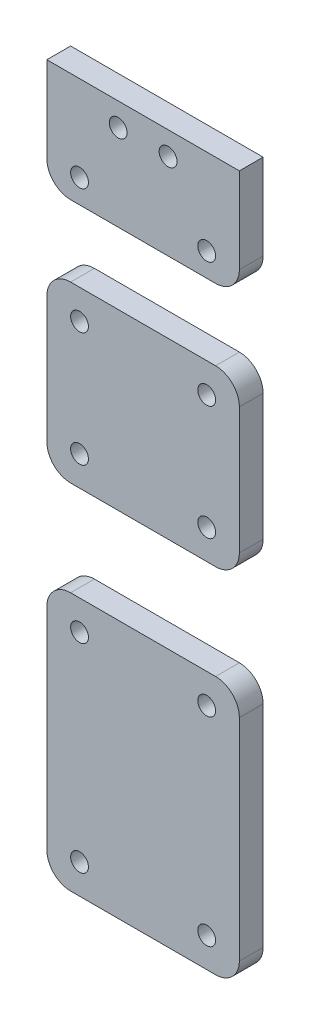
SolidWorks part; units mm, degrees
ref_plane "Front Plane" through (0, 0, 0) normal (0, 0, 1) x (1, 0, 0)
ref_plane "Top Plane" through (0, 0, 0) normal (0, 1, 0) x (1, 0, 0)
ref_plane "Right Plane" through (0, 0, 0) normal (1, 0, 0) x (0, 0, -1)
sketch "Sketch1" plane through (0, 0, 0) normal (0, 0, 1) x (1, 0, 0)
  line L0 (0, 1.5) -> (0, 14) construction
  line L1 (16.2, 1.5) -> (16.2, 14) construction
  line L2 (2, 47.74) -> (4, 47.74)
  line L3 (0, 1.5) -> (16.2, 1.5) construction
  line L4 (0, 14) -> (4, 14) construction
  line L5 (2, 26) -> (4, 26)
  line L6 (16.2, 85.59) -> (0, 85.59)
  line L7 (2, 70.385) -> (4, 70.385)
  line L8 (2, 55.74) -> (4, 55.74)
  line L9 (0, 28) -> (0, 45.74)
  line L10 (2, 76.385) -> (4, 76.385)
  line L11 (16.2, 28) -> (16.2, 45.74)
  line L12 (16.2, 57.74) -> (16.2, 68.385)
  line L13 (0, 57.74) -> (0, 68.385)
  line L14 (16.2, 78.385) -> (16.2, 85.59)
  line L15 (0, 78.385) -> (0, 85.59)
  line L16 (6, 70.385) -> (6, 76.385)
  line L17 (4, 55.74) -> (4, 47.74)
  line L18 (4, 70.385) -> (4, 76.385)
  line L19 (6, 55.74) -> (6, 47.74)
  line L20 (4, 26) -> (4, 14)
  line L21 (6, 26) -> (6, 14)
  line L22 (8.1, 1.5) -> (8.1, 85.59) construction
  line L23 (10.2, 26) -> (10.2, 14)
  line L24 (12.2, 26) -> (12.2, 14)
  line L25 (10.2, 55.74) -> (10.2, 47.74)
  line L26 (12.2, 55.74) -> (12.2, 47.74)
  line L27 (10.2, 70.385) -> (10.2, 76.385)
  line L28 (12.2, 70.385) -> (12.2, 76.385)
  line L29 (6, 26) -> (10.2, 26)
  line L30 (6, 14) -> (10.2, 14) construction
  line L31 (12.2, 14) -> (16.2, 14) construction
  line L32 (12.2, 26) -> (14.2, 26)
  line L33 (12.2, 47.74) -> (14.2, 47.74)
  line L34 (6, 47.74) -> (10.2, 47.74)
  line L35 (12.2, 76.385) -> (14.2, 76.385)
  line L36 (6, 76.385) -> (10.2, 76.385)
  line L37 (6, 70.385) -> (10.2, 70.385)
  line L38 (12.2, 70.385) -> (14.2, 70.385)
  line L39 (12.2, 55.74) -> (14.2, 55.74)
  line L40 (6, 55.74) -> (10.2, 55.74)
  line L41 (4, 14) -> (6, 14)
  line L42 (10.2, 14) -> (12.2, 14)
  circle A0 centre (13.45, 45.24) radius 0.75
  circle A1 centre (2.75, 67.885) radius 0.75
  circle A2 centre (13.45, 58.24) radius 0.75
  circle A3 centre (13.45, 78.385) radius 0.75
  circle A4 centre (2.75, 28.5) radius 0.75
  circle A5 centre (2.75, 78.385) radius 0.75
  circle A6 centre (2.75, 58.24) radius 0.75
  circle A7 centre (2.85, 11.5) radius 0.75 construction
  circle A8 centre (13.35, 11.5) radius 0.75 construction
  circle A9 centre (13.35, 5.5) radius 0.75 construction
  circle A10 centre (2.85, 5.5) radius 0.75 construction
  circle A11 centre (6, 83.635) radius 0.75
  circle A12 centre (13.45, 28.5) radius 0.75
  circle A13 centre (13.45, 67.885) radius 0.75
  circle A14 centre (10.2, 83.635) radius 0.75
  circle A15 centre (2.75, 45.24) radius 0.75
  arc A16 (0, 28) -> (2, 26) centre (2, 28) ccw
  arc A17 (16.2, 28) -> (14.2, 26) centre (14.2, 28) cw
  arc A18 (16.2, 45.74) -> (14.2, 47.74) centre (14.2, 45.74) ccw
  arc A19 (0, 45.74) -> (2, 47.74) centre (2, 45.74) cw
  arc A20 (0, 57.74) -> (2, 55.74) centre (2, 57.74) ccw
  arc A21 (16.2, 57.74) -> (14.2, 55.74) centre (14.2, 57.74) cw
  arc A22 (0, 68.385) -> (2, 70.385) centre (2, 68.385) cw
  arc A23 (16.2, 68.385) -> (14.2, 70.385) centre (14.2, 68.385) ccw
  arc A24 (16.2, 78.385) -> (14.2, 76.385) centre (14.2, 78.385) cw
  arc A25 (2, 76.385) -> (0, 78.385) centre (2, 78.385) cw
  point P77 (0, 26)
  point P80 (16.2, 26)
  point P83 (16.2, 47.74)
  point P86 (0, 47.74)
  point P89 (0, 55.74)
  point P92 (16.2, 55.74)
  point P95 (0, 70.385)
  point P98 (16.2, 70.385)
  point P101 (16.2, 76.385)
  point P104 (0, 76.385)
  dimension "D1" = 4
  dimension "D40" = 2
  dimension "D41" = 1.5
  dimension "D2" = 4
  dimension "D3" = 6
  dimension "D4" = 6
  dimension "D5" = 2.5
  dimension "D6" = 12
  dimension "D7" = 2.85
  dimension "D8" = 2.85
  dimension "D9" = 2.85
  dimension "D10" = 16.2
  dimension "D11" = 21.74
  dimension "D12" = 2.75
  dimension "D13" = 2.75
  dimension "D14" = 2.75
  dimension "D15" = 2.75
  dimension "D16" = 2.5
  dimension "D17" = 2.5
  dimension "D18" = 2.5
  dimension "D19" = 2.5
  dimension "D20" = 8
  dimension "D21" = 14.645
  dimension "D22" = 2.75
  dimension "D23" = 2.75
  dimension "D24" = 2.5
  dimension "D25" = 2.5
  dimension "D26" = 2.5
  dimension "D27" = 2.5
  dimension "D28" = 2.75
  dimension "D29" = 2.75
  dimension "D30" = 6
  dimension "D31" = 9.205
  dimension "D32" = 2.75
  dimension "D33" = 6
  dimension "D34" = 2
  dimension "D35" = 7.25
  dimension "D36" = 2
  dimension "D37" = 7.25
  dimension "D38" = 6
  dimension "D39" = 2.75
extrude "Boss-Extrude1" add sketch "Sketch1" along normal blind 2
sketch "Sketch2" plane through (0, 0, 2) normal (0, 0, 1) x (1, 0, 0)
  line L0 (4, 76.385) -> (12.2, 76.385)
  line L1 (12.2, 76.385) -> (12.2, 70.385)
  line L2 (12.2, 70.385) -> (4, 70.385)
  line L3 (4, 70.385) -> (4, 76.385)
  line L4 (4, 55.74) -> (12.2, 55.74)
  line L5 (12.2, 55.74) -> (12.2, 47.74)
  line L6 (12.2, 47.74) -> (4, 47.74)
  line L7 (4, 47.74) -> (4, 55.74)
  line L8 (4, 26) -> (12.2, 26)
  line L9 (12.2, 26) -> (12.2, 14)
  line L10 (12.2, 14) -> (4, 14)
  line L11 (4, 14) -> (4, 26)
extrude "Cut-Extrude1" cut sketch "Sketch2" against normal up to surface (2 mm away) up to face at (8.1, 73.385, 0)
equation "\"D11@Sketch1\"= \"HL@parametersSketch@prostheticParameters.SLDPRT\" * 0.204 - 4 - 12 'Pinky PIP Length"
equation "\"D21@Sketch1\"= \"HL@parametersSketch@prostheticParameters.SLDPRT\" * 0.117 - 4 - 3 'Pinky MIP Length"
equation "\"D31@Sketch1\"= \"HL@parametersSketch@prostheticParameters.SLDPRT\" * 0.093 - 3 - 5'Pinky DIP Length"
equation "\"D10@Sketch1\"= \"fingerWidth@parametersSketch@prostheticParameters.SLDPRT\"'Pinky Width"
